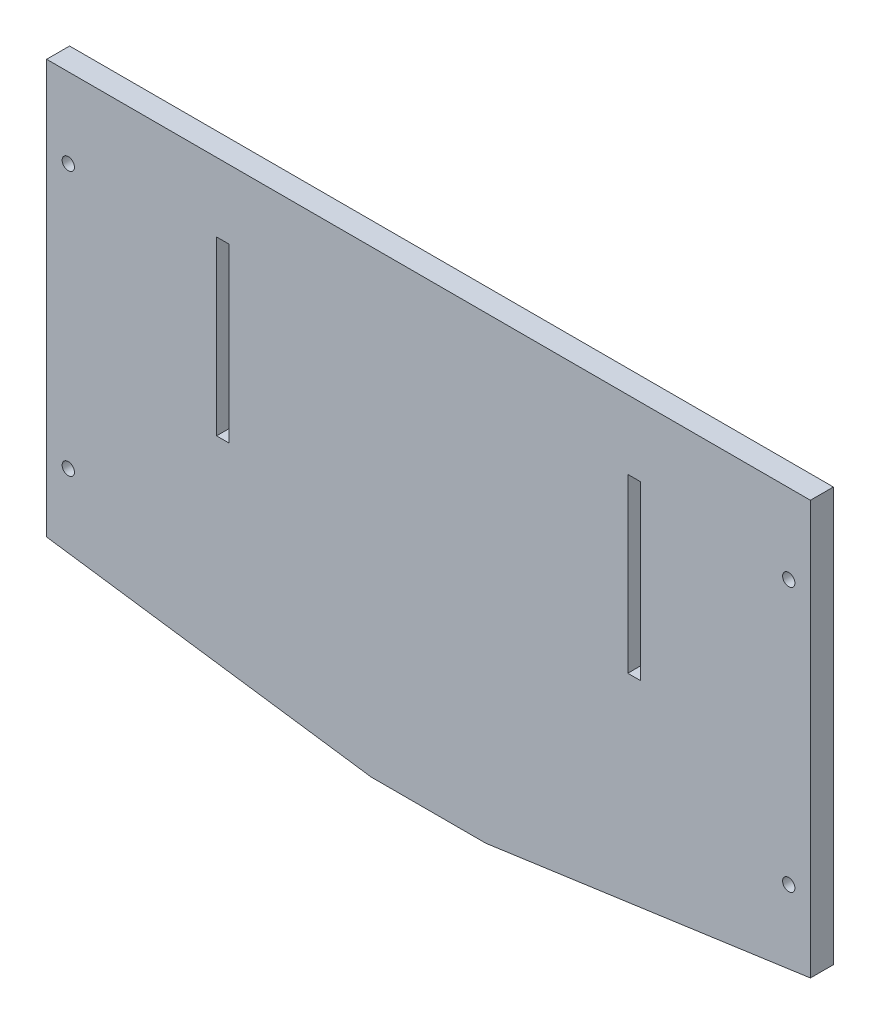
SolidWorks part; units mm, degrees
material "Acrylic (Medium-high impact)"
ref_plane "Front Plane" through (0, 0, 0) normal (0, 0, 1) x (1, 0, 0)
ref_plane "Top Plane" through (0, 0, 0) normal (0, 1, 0) x (1, 0, 0)
ref_plane "Right Plane" through (0, 0, 0) normal (1, 0, 0) x (0, 0, -1)
sketch "Sketch1" plane through (0, 0, 0) normal (0, 0, 1) x (1, 0, 0)
  line L1 (211.1756, 127) -> (0, 127)
  line L2 (211.1756, 127) -> (211.1756, 0)
  line L3 (211.1756, 0) -> (0, 0)
  line L4 (0, 127) -> (0, 0)
  line L5 (211.1756, 127) -> (0, 0) construction
  line L6 (211.1756, 0) -> (0, 127) construction
  point P0 (105.5878, 63.5)
  dimension "D1" = 127
  dimension "D2" = 211.1756
extrude "Boss-Extrude1" add sketch "Sketch1" along normal blind 6.35
hole_wizard "M3 Clearance Hole1" positions "Sketch2" profile "Sketch3" hole size "M3" standard "ANSI Metric" end condition through all
sketch "Sketch2" plane through (0, 0, 6.35) normal (0, 0, 1) x (1, 0, 0)
  line L0 (0, 127) -> (0, 0) construction
  line L1 (211.1756, 127) -> (0, 127) construction
  line L2 (211.1756, 0) -> (211.1756, 127) construction
  point P0 (5.9944, 105.0036)
  point P2 (5.9944, 31.9786)
  point P4 (205.1812, 31.9786)
  point P6 (205.1812, 105.0036)
  dimension "D1" = 5.9944
  dimension "D2" = 21.9964
  dimension "D3" = 5.9944
  dimension "D4" = 73.025
sketch "Sketch3" plane through (5.9944, 105.0036, 6.35) normal (1, 0, 0) x (0, -1, 0)
  line L0 (0, 0) -> (0, 6.35)
  line L1 (0, 6.35) -> (1.7, 6.35)
  line L2 (1.7, 6.35) -> (1.7, 0)
  line L5 (1.7, 0) -> (0, 0)
  line L11 (0, -6.35) -> (0, 107.95) construction
  dimension "Thru Hole Dia." = 3.4
  dimension "Thru Hole Depth" = 6.35
sketch "Sketch4" plane through (0, 0, 6.35) normal (0, 0, 1) x (1, 0, 0)
  line L0 (0, 127) -> (0, 0) construction
  line L1 (46.99, 107.95) -> (50.4952, 107.95)
  line L2 (46.99, 107.95) -> (46.99, 60.325)
  line L3 (46.99, 60.325) -> (50.4952, 60.325)
  line L4 (50.4952, 107.95) -> (50.4952, 60.325)
  line L5 (160.6804, 107.95) -> (164.1856, 107.95)
  line L6 (160.6804, 107.95) -> (160.6804, 60.325)
  line L7 (160.6804, 60.325) -> (164.1856, 60.325)
  line L8 (164.1856, 107.95) -> (164.1856, 60.325)
  line L9 (211.1756, 0) -> (211.1756, 127) construction
  line L10 (211.1756, 127) -> (0, 127) construction
  dimension "D1" = 3.5052
  dimension "D2" = 47.625
  dimension "D3" = 46.99
  dimension "D4" = 46.99
  dimension "D5" = 19.05
extrude "Cut-Extrude1" cut sketch "Sketch4" against normal through all
sketch "Sketch5" plane through (0, 0, 6.35) normal (0, 0, 1) x (1, 0, 0)
  line L0 (0, 12.6083) -> (89.7128, 0)
  line L1 (0, 127) -> (0, 0) construction
  line L2 (0, 0) -> (211.1756, 0) construction
  line L3 (89.7128, 0) -> (0, 0)
  line L4 (0, 0) -> (0, 12.6083)
  line L5 (121.4628, 0) -> (211.1756, 0)
  line L6 (211.1756, 0) -> (211.1756, 12.6083)
  line L7 (211.1756, 0) -> (211.1756, 127) construction
  line L8 (211.1756, 12.6083) -> (121.4628, 0)
  dimension "D1" = 8
  dimension "D2" = 8
  dimension "D3" = 31.75
extrude "Cut-Extrude2" cut sketch "Sketch5" against normal through all
